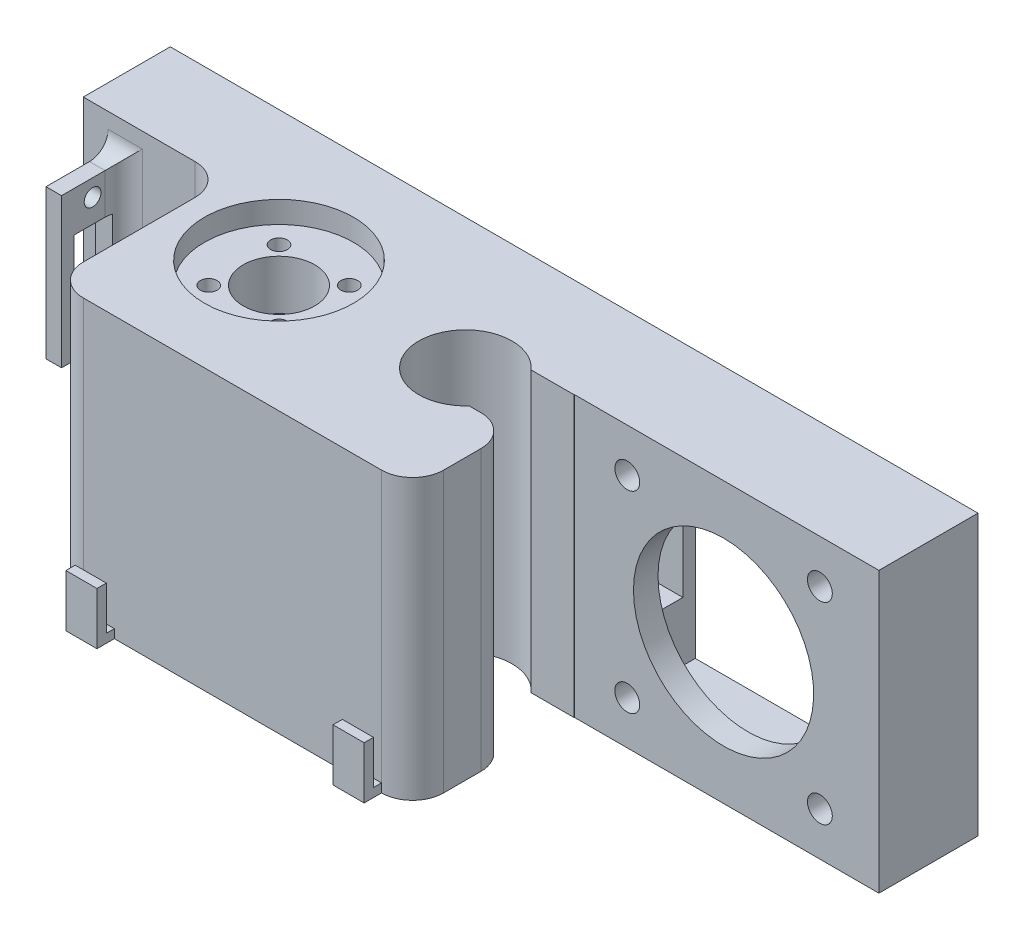
SolidWorks part; units mm, degrees
ref_plane "Front Plane" through (0, 0, 0) normal (0, 0, 1) x (1, 0, 0)
ref_plane "Top Plane" through (0, 0, 0) normal (0, 1, 0) x (1, 0, 0)
ref_plane "Right Plane" through (0, 0, 0) normal (1, 0, 0) x (0, 0, -1)
sketch "Sketch1" plane through (0, 0, 0) normal (0, 0, 1) x (1, 0, 0)
  line L1 (0, 0) -> (130, 0)
  line L2 (0, 0) -> (0, 45)
  line L3 (0, 45) -> (130, 45)
  line L4 (130, 0) -> (130, 45)
  dimension "D1" = 45
  dimension "D2" = 130
extrude "Boss-Extrude1" add sketch "Sketch1" along normal blind 42
sketch "Sketch2" plane through (0, 0, 0) normal (-1, 0, 0) x (0, 0, 1)
  line L0 (42, 22.5) -> (0, 22.5) construction
  line L5 (42, 45) -> (42, 0) construction
  line L6 (0, 45) -> (0, 0) construction
  line L8 (2, 11.5) -> (12, 11.5)
  line L9 (2, 11.5) -> (2, 33.5)
  line L10 (2, 33.5) -> (12, 33.5)
  line L11 (12, 11.5) -> (12, 33.5)
  line L12 (2, 11.5) -> (12, 33.5) construction
  line L13 (2, 33.5) -> (12, 11.5) construction
  point P10 (7, 22.5)
  dimension "D1" = 2
  dimension "D2" = 22
  dimension "D3" = 10
extrude "Cut-Extrude1" cut sketch "Sketch2" against normal blind 115
sketch "Sketch3" plane through (0, 0, 0) normal (0, 0, -1) x (-1, 0, 0)
  line L1 (-120.5, 38) -> (-89.5, 38) construction
  line L2 (-120.5, 38) -> (-120.5, 7) construction
  line L3 (-120.5, 7) -> (-89.5, 7) construction
  line L4 (-89.5, 38) -> (-89.5, 7) construction
  line L5 (-120.5, 38) -> (-89.5, 7) construction
  line L6 (-120.5, 7) -> (-89.5, 38) construction
  line L7 (-125.5, 43) -> (-84.5, 43)
  line L8 (-125.5, 43) -> (-125.5, 2)
  line L9 (-125.5, 2) -> (-84.5, 2)
  line L10 (-84.5, 43) -> (-84.5, 2)
  line L11 (-125.5, 43) -> (-84.5, 2) construction
  line L12 (-125.5, 2) -> (-84.5, 43) construction
  point P4 (-105, 22.5)
  point P11 (-105, 22.5)
  dimension "D1" = 5
  dimension "D2" = 5
extrude "Cut-Extrude2" cut sketch "Sketch3" against normal blind 12
sketch "Sketch5" plane through (0, 0, 42) normal (0, 0, 1) x (1, 0, 0)
  line L0 (0, 0) -> (130, 0) construction
  line L1 (130, 45) -> (81, 45)
  line L2 (130, 45) -> (130, 0)
  line L3 (130, 0) -> (81, 0)
  line L4 (81, 45) -> (81, 0)
  line L5 (130, 45) -> (81, 0) construction
  line L6 (130, 0) -> (81, 45) construction
  point P4 (105.5, 22.5)
  dimension "D1" = 49
extrude "Cut-Extrude3" cut sketch "Sketch5" against normal up to surface (26.05 mm away)
sketch "Sketch6" plane through (0, 0, 0) normal (0, 0, -1) x (-1, 0, 0)
  line L1 (-120.5, 38) -> (-89.5, 38) construction
  line L2 (-120.5, 38) -> (-120.5, 7) construction
  line L3 (-120.5, 7) -> (-89.5, 7) construction
  line L4 (-89.5, 38) -> (-89.5, 7) construction
  line L5 (-120.5, 38) -> (-89.5, 7) construction
  line L6 (-120.5, 7) -> (-89.5, 38) construction
  circle A0 centre (-120.5, 38) radius 2
  circle A1 centre (-89.5, 38) radius 2
  circle A2 centre (-89.5, 7) radius 2
  circle A3 centre (-120.5, 7) radius 2
  point P4 (-105, 22.5)
  dimension "D1" = 4
  dimension "D2" = 4
  dimension "D3" = 4
  dimension "D4" = 4
extrude "Cut-Extrude4" cut sketch "Sketch6" against normal through all
sketch "Sketch7" plane through (0, 45, 0) normal (0, 1, 0) x (1, 0, 0)
  circle A0 centre (38.5, -21) radius 12
  dimension "D1" = 24
extrude "Cut-Extrude5" cut sketch "Sketch7" against normal blind 3.5
sketch "Sketch8" plane through (0, 45, 0) normal (0, 1, 0) x (1, 0, 0)
  circle A0 centre (68.5, -21) radius 7.5
  dimension "D1" = 15
extrude "Cut-Extrude6" cut sketch "Sketch8" against normal through all
sketch "Sketch10" plane through (0, 45, 0) normal (0, 1, 0) x (1, 0, 0)
  line L1 (0, -42) -> (23, -42)
  line L2 (0, -42) -> (0, -14)
  line L3 (0, -14) -> (23, -14)
  line L4 (23, -42) -> (23, -14)
  line L5 (0, -42) -> (23, -14) construction
  line L6 (0, -14) -> (23, -42) construction
  point P4 (11.5, -28)
  dimension "D1" = 28
  dimension "D2" = 23
extrude "Cut-Extrude7" cut sketch "Sketch10" against normal through all
fillet "Fillet1" radius 5 2 edges at (23, 22.5, 42) (81, 22.5, 42)
sketch "Sketch11" plane through (0, 41.5, 0) normal (0, 1, 0) x (1, 0, 0)
  circle A0 centre (38.5, -21) radius 5.75
  dimension "D1" = 11.5
extrude "Cut-Extrude8" cut sketch "Sketch11" against normal through all
sketch "Sketch12" plane through (0, 41.5, 0) normal (0, 1, 0) x (1, 0, 0)
  circle A0 centre (32.8431, -15.3431) radius 1.35
  circle A1 centre (44.1569, -15.3431) radius 1.35
  circle A2 centre (44.1569, -26.6569) radius 1.35
  circle A3 centre (32.8431, -26.6569) radius 1.35
  dimension "D1" = 2.7
extrude "Cut-Extrude9" cut sketch "Sketch12" against normal blind 20
sketch "Sketch14" plane through (0, 0, 0) normal (0, 0, -1) x (-1, 0, 0)
  line L0 (0, 22.5) -> (-84.5, 22.5) construction
  line L1 (-75, 7.5) -> (-15, 7.5) construction
  line L2 (-75, 7.5) -> (-75, 37.5) construction
  line L3 (-75, 37.5) -> (-15, 37.5) construction
  line L4 (-15, 7.5) -> (-15, 37.5) construction
  line L5 (-75, 7.5) -> (-15, 37.5) construction
  line L6 (-75, 37.5) -> (-15, 7.5) construction
  line L7 (0, 45) -> (0, 0) construction
  line L8 (-84.5, 2) -> (-84.5, 43) construction
  circle A0 centre (-75, 37.5) radius 1.75
  circle A1 centre (-15, 37.5) radius 1.75
  circle A2 centre (-15, 7.5) radius 1.75
  circle A3 centre (-75, 7.5) radius 1.75
  point P0 (-45, 22.5)
  dimension "D4" = 3.5
  dimension "D1" = 60
  dimension "D2" = 30
  dimension "D3" = 15
extrude "Cut-Extrude11" cut sketch "Sketch14" against normal blind 12
sketch "Sketch15" plane through (0, 45, 0) normal (0, 1, 0) x (1, 0, 0)
  line L0 (61, -21) -> (86.2394, -21) construction
  line L2 (98.575, -16) -> (66.113, -16)
  line L3 (98.575, -16) -> (98.575, -26)
  line L4 (98.575, -26) -> (66.113, -26)
  line L5 (66.113, -16) -> (66.113, -26)
  line L6 (98.575, -16) -> (66.113, -26) construction
  line L7 (98.575, -26) -> (66.113, -16) construction
  circle A0 centre (68.5, -21) radius 7.5 construction
  point P5 (82.344, -21)
  dimension "D1" = 10
extrude "Cut-Extrude12" cut sketch "Sketch15" against normal through all
fillet "Fillet2" radius 5 1 edges at (81, 22.5, 26)
fillet "Fillet3" radius 5 1 edges at (23, 22.5, 14)
sketch "Sketch16" plane through (0, 0, 0) normal (0, -1, 0) x (1, 0, 0)
  circle A0 centre (38.5, 21) radius 12.5
  dimension "D1" = 25
extrude "Cut-Extrude13" cut sketch "Sketch16" against normal up to surface (33.5 mm away) up to face at (42.25, 33.5, 7)
sketch "Sketch17" plane through (0, 0, 14) normal (0, 0, 1) x (1, 0, 0)
  line L1 (4, 39.5) -> (6.5, 39.5)
  line L2 (4, 39.5) -> (4, 15.5)
  line L3 (4, 15.5) -> (6.5, 15.5)
  line L4 (6.5, 39.5) -> (6.5, 15.5)
  line L5 (4, 39.5) -> (6.5, 15.5) construction
  line L6 (4, 15.5) -> (6.5, 39.5) construction
  point P4 (5.25, 27.5)
  dimension "D1" = 24
  dimension "D2" = 2.5
extrude "Boss-Extrude2" add sketch "Sketch17" along normal blind 10
sketch "Sketch18" plane through (4, 0, 0) normal (-1, 0, 0) x (0, 0, 1)
  circle A0 centre (19, 36.775) radius 1.35
  circle A1 centre (19, 17.725) radius 1.35
  dimension "D1" = 2.7
extrude "Cut-Extrude14" cut sketch "Sketch18" against normal blind 10
fillet "Fillet4" radius 3 1 edges at (6.5, 27.5, 14)
fillet "Fillet5" radius 3 2 edges at (6.75, 39.5, 14) (6.75, 15.5, 14)
sketch "Sketch20" plane through (0, 0, 42) normal (0, 0, 1) x (1, 0, 0)
  line L1 (28, 0) -> (33, 0)
  line L2 (28, 0) -> (28, 1.4)
  line L3 (28, 1.4) -> (33, 1.4)
  line L4 (33, 0) -> (33, 1.4)
  line L5 (28, 0) -> (33, 1.4) construction
  line L6 (28, 1.4) -> (33, 0) construction
  line L7 (76, 0) -> (71, 0)
  line L8 (76, 0) -> (76, 1.4)
  line L9 (76, 1.4) -> (71, 1.4)
  line L10 (71, 0) -> (71, 1.4)
  line L11 (76, 0) -> (71, 1.4) construction
  line L12 (76, 1.4) -> (71, 0) construction
  point P4 (30.5, 0.7)
  point P10 (73.5, 0.7)
  dimension "D1" = 1.4
  dimension "D2" = 5
  dimension "D3" = 5
  dimension "D4" = 1.4
extrude "Boss-Extrude3" add sketch "Sketch20" along normal blind 2.8
sketch "Sketch22" plane through (23, 0, 0) normal (-1, 0, 0) x (0, 0, 1)
  line L0 (28, 45) -> (28, 0) construction
  line L1 (25.5, 0) -> (30.5, 0)
  line L2 (25.5, 0) -> (25.5, 1.4)
  line L3 (25.5, 1.4) -> (30.5, 1.4)
  line L4 (30.5, 0) -> (30.5, 1.4)
  line L5 (25.5, 0) -> (30.5, 1.4) construction
  line L6 (25.5, 1.4) -> (30.5, 0) construction
  line L7 (37, 45) -> (19, 45) construction
  line L8 (37, 0) -> (19, 0) construction
  point P4 (28, 0.7)
  dimension "D1" = 1.4
  dimension "D2" = 5
extrude "Boss-Extrude4" add sketch "Sketch22" along normal blind 2.8
sketch "Sketch25" plane through (0, 1.4, 0) normal (0, 1, 0) x (1, 0, 0)
  line L0 (20.2, -25.5) -> (23, -25.5) construction
  line L1 (20.2, -25.5) -> (21.7, -25.5)
  line L2 (20.2, -25.5) -> (20.2, -30.5)
  line L3 (20.2, -30.5) -> (21.7, -30.5)
  line L4 (21.7, -25.5) -> (21.7, -30.5)
  line L5 (20.2, -25.5) -> (21.7, -30.5) construction
  line L6 (20.2, -30.5) -> (21.7, -25.5) construction
  line L7 (20.2, -30.5) -> (23, -30.5) construction
  line L8 (23, -37) -> (23, -19) construction
  line L9 (76, -44.8) -> (76, -42) construction
  line L10 (76, -43.3) -> (71, -43.3)
  line L11 (76, -43.3) -> (76, -44.8)
  line L12 (76, -44.8) -> (71, -44.8)
  line L13 (71, -43.3) -> (71, -44.8)
  line L14 (76, -43.3) -> (71, -44.8) construction
  line L15 (76, -44.8) -> (71, -43.3) construction
  line L16 (71, -44.8) -> (71, -42) construction
  line L17 (33, -44.8) -> (33, -42) construction
  line L18 (33, -43.3) -> (28, -43.3)
  line L19 (33, -43.3) -> (33, -44.8)
  line L20 (33, -44.8) -> (28, -44.8)
  line L21 (28, -43.3) -> (28, -44.8)
  line L22 (33, -43.3) -> (28, -44.8) construction
  line L23 (33, -44.8) -> (28, -43.3) construction
  line L24 (28, -44.8) -> (28, -42) construction
  line L25 (76, -42) -> (71, -42) construction
  line L26 (33, -42) -> (28, -42) construction
  point P4 (20.95, -28)
  point P15 (73.5, -44.05)
  point P24 (30.5, -44.05)
  dimension "D1" = 1.3
  dimension "D2" = 1.5
  dimension "D3" = 1.5
  dimension "D4" = 1.3
  dimension "D5" = 1.5
  dimension "D6" = 1.3
extrude "Boss-Extrude5" add sketch "Sketch25" along normal blind 7
sketch "Sketch26" plane through (0, 0, 12) normal (0, 0, -1) x (-1, 0, 0)
  line L0 (-105, 43) -> (-105, 2) construction
  line L1 (-84.5, 43) -> (-125.5, 43) construction
  line L2 (-125.5, 2) -> (-84.5, 2) construction
  line L3 (-125.5, 22.5) -> (-84.5, 22.5) construction
  line L4 (-125.5, 43) -> (-125.5, 2) construction
  line L5 (-84.5, 2) -> (-84.5, 43) construction
  circle A0 centre (-105, 22.5) radius 14.5
  dimension "D1" = 29
extrude "Cut-Extrude15" cut sketch "Sketch26" against normal blind 10
sketch "Sketch27" plane through (4, 0, 0) normal (-1, 0, 0) x (0, 0, 1)
  line L0 (19, 45) -> (19, 0) construction
  line L1 (16, 22) -> (22, 22)
  line L2 (16, 22) -> (16, 33)
  line L3 (16, 33) -> (22, 33)
  line L4 (22, 22) -> (22, 33)
  line L5 (16, 22) -> (22, 33) construction
  line L6 (16, 33) -> (22, 22) construction
  point P0 (19, 27.5)
  dimension "D1" = 11
  dimension "D2" = 6
extrude "Cut-Extrude16" cut sketch "Sketch27" against normal blind 10
